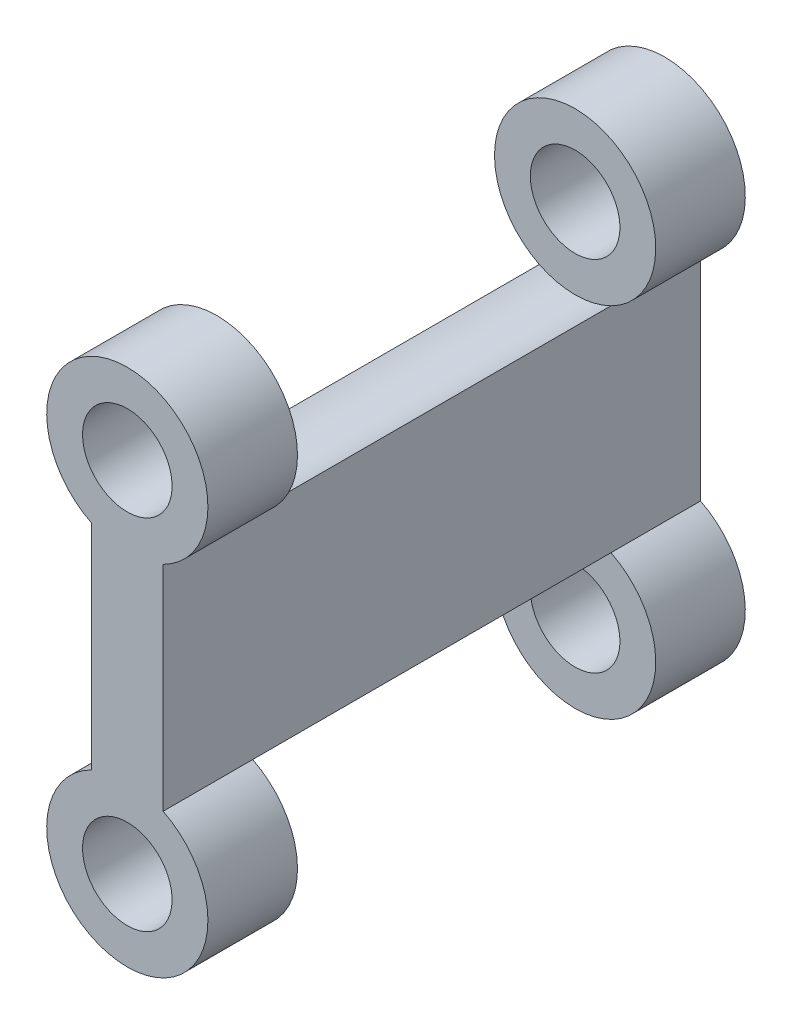
SolidWorks part; units mm, degrees
ref_plane "Front Plane" through (0, 0, 0) normal (0, 0, 1) x (1, 0, 0)
ref_plane "Top Plane" through (0, 0, 0) normal (0, 1, 0) x (1, 0, 0)
ref_plane "Right Plane" through (0, 0, 0) normal (1, 0, 0) x (0, 0, -1)
sketch "Sketch1" plane through (0, 0, 0) normal (0, 0, 1) x (1, 0, 0)
  line L0 (0, 25.4) -> (0, 0) construction
  line L1 (-2.54, 23.495) -> (-2.54, 1.905)
  line L2 (2.54, 23.495) -> (2.54, 1.905)
  circle A0 centre (0, 0) radius 3.175
  circle A1 centre (0, 25.4) radius 3.175
  circle A2 centre (0, 25.4) radius 5.715
  circle A3 centre (0, 0) radius 5.715
  dimension "D1" = 6.35
  dimension "D2" = 25.4
  dimension "D3" = 2.54
  dimension "D4" = 2.54
extrude "Boss-Extrude1" add sketch "Sketch1" along normal mid plane 38.1 contours L2 A2 L1 A1 | L0 A1 L1 A2 | A1 L0 A2 L2 | A2 L0 A3 L2 | L0 A3 L1 A0 | L0 A2 L1 A3 | A3 L0 A0 L2 | L1 A3 L2 A0 region at (1.3173, 21.2617, 0) region at (-1.3173, 21.2617, 0) region at (1.2874, 12.7, 0) region at (-1.2874, 12.7, 0) region at (-2.6975, 21.8877, 0) region at (1.3173, 4.1383, 0) region at (-1.3173, 4.1383, 0) region at (4.723, 2.9291, 0)
extrude "Cut-Extrude2" cut sketch "Sketch1<3>" against normal mid plane 25.4 contours A3 L0 A0 L2 | L0 A3 L1 A0 | L1 A3 L2 A0 | L2 A2 L1 A1 | A1 L0 A2 L2 | L0 A1 L1 A2 region at (1.3173, 21.2617, 0) region at (-1.3173, 21.2617, 0) region at (-2.6975, 21.8877, 0) region at (1.3173, 4.1383, 0) region at (-1.3173, 4.1383, 0) region at (4.723, 2.9291, 0)
sketch "Sketch1<3>" plane through (0, 0, 0) normal (0, 0, 1) x (1, 0, 0) same geometry as "Sketch1"
